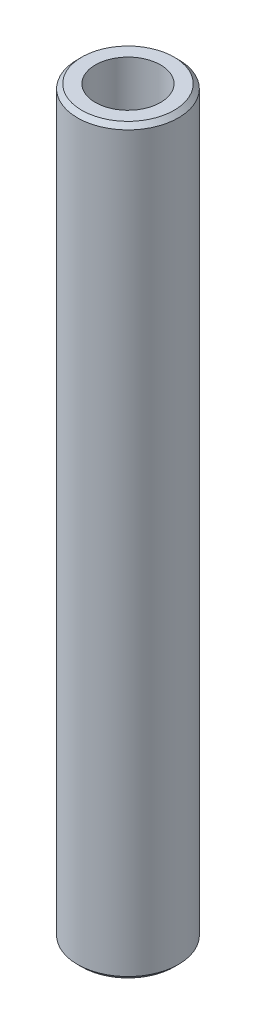
SolidWorks part; units mm, degrees
ref_plane "Front Plane" through (0, 0, 0) normal (0, 0, 1) x (1, 0, 0)
ref_plane "Top Plane" through (0, 0, 0) normal (0, 1, 0) x (1, 0, 0)
ref_plane "Right Plane" through (0, 0, 0) normal (1, 0, 0) x (0, 0, -1)
sketch "Sketch1" plane through (0, 0, 0) normal (0, 1, 0) x (1, 0, 0)
  circle A0 centre (0, 0) radius 37.5
  dimension "SHAFT_OD" = 75
extrude "Boss-Extrude1" add sketch "Sketch1" along normal blind 550.9412
sketch "Sketch2" plane through (0, 0, 0) normal (0, 1, 0) x (1, 0, 0)
  circle A0 centre (0, 0) radius 24.216
  dimension "BORE_D" = 48.4321
extrude "Cut-Extrude1" cut sketch "Sketch2" along normal through all
chamfer "Chamfer1" distance 3.2262 angle 45 2 edges at (0, 550.9412, 37.5) (0, 0, 37.5)
